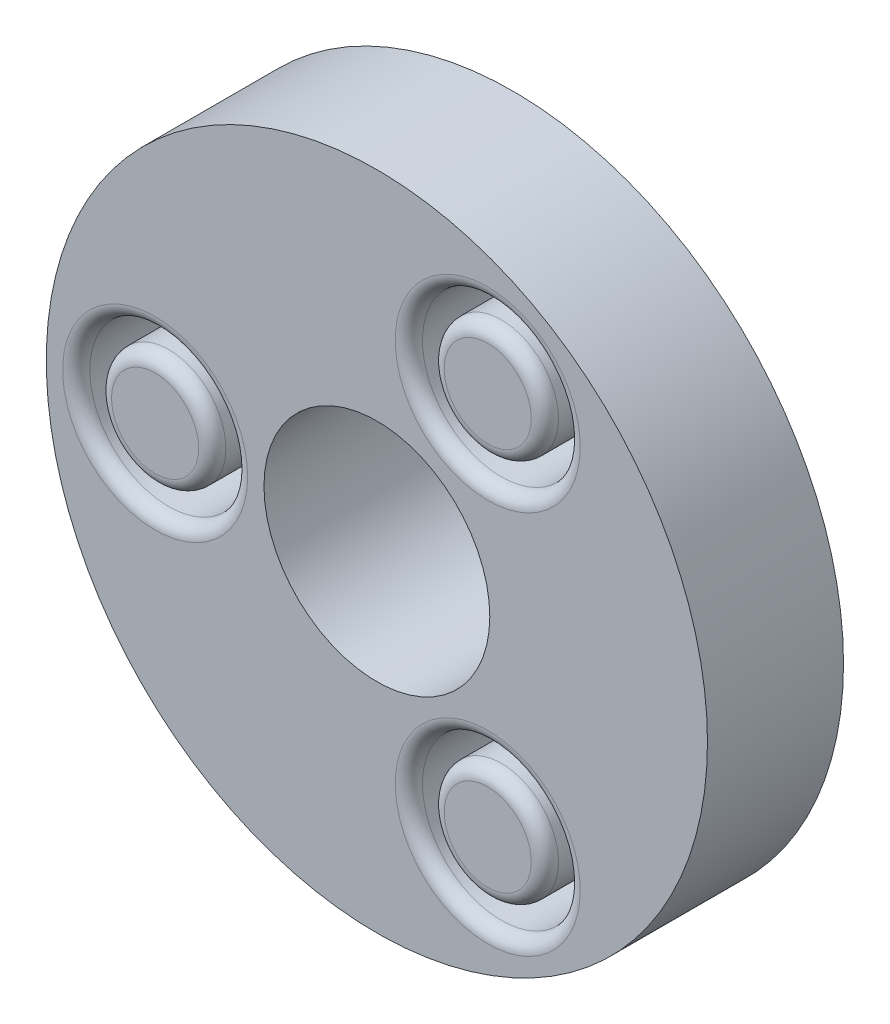
SolidWorks part; units mm, degrees
ref_plane "Front Plane" through (0, 0, 0) normal (0, 0, 1) x (1, 0, 0)
ref_plane "Top Plane" through (0, 0, 0) normal (0, 1, 0) x (1, 0, 0)
ref_plane "Right Plane" through (0, 0, 0) normal (1, 0, 0) x (0, 0, -1)
sketch "Sketch1" plane through (0, 0, 0) normal (0, 0, 1) x (1, 0, 0)
  circle A0 centre (0, 0) radius 4.15
  circle A1 centre (0, 0) radius 6
  dimension "D1" = 8.3
  dimension "D2" = 12
extrude "Boss-Extrude1" add sketch "Sketch1" along normal blind 2
sketch "Sketch2" plane through (0, 0, 2) normal (0, 0, 1) x (1, 0, 0)
  line L0 (-4.15, 0) -> (-12.15, 0) construction
  circle A0 centre (0, 0) radius 12.15
  circle A1 centre (0, 0) radius 4.15
  circle A2 centre (0, 0) radius 4.15 construction
  dimension "D1" = 8
extrude "Boss-Extrude2" add sketch "Sketch2" along normal blind 5
sketch "Sketch3" plane through (0, 0, 7) normal (0, 0, 1) x (1, 0, 0)
  line L0 (-4.15, 0) -> (-12.15, 0) construction
  circle A0 centre (0, 0) radius 4.15 construction
  circle A1 centre (0, 0) radius 12.15 construction
  circle A2 centre (-8.15, 0) radius 2.9
  circle A3 centre (-8.15, 0) radius 2.1
  circle A4 centre (4.075, 7.0581) radius 2.9
  circle A5 centre (4.075, 7.0581) radius 2.1
  circle A6 centre (4.075, -7.0581) radius 2.9
  circle A7 centre (4.075, -7.0581) radius 2.1
  point P19 (0, 0)
  dimension "D1" = 5.8
  dimension "D2" = 4.2
  dimension "D3" = 3
extrude "Cut-Extrude1" cut sketch "Sketch3" against normal blind 4
fillet "Fillet1" radius 0.5 6 edges at (6.975, -7.0581, 7) (-5.25, 0, 7) (6.175, 7.0581, 7) (6.175, -7.0581, 7) (-6.05, 0, 7) (6.975, 7.0581, 7)
chamfer "Chamfer1" distance 2 angle 45 1 edges at (6, 0, 2)
